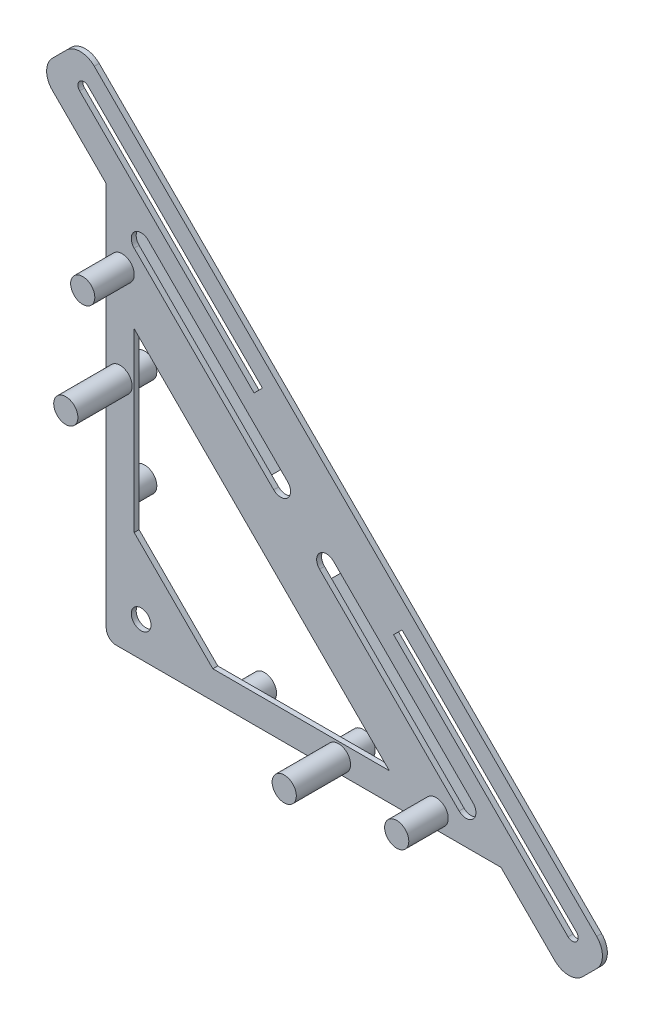
SolidWorks part; units mm, degrees
ref_plane "Front Plane" through (0, 0, 0) normal (0, 0, 1) x (1, 0, 0)
ref_plane "Top Plane" through (0, 0, 0) normal (0, 1, 0) x (1, 0, 0)
ref_plane "Right Plane" through (0, 0, 0) normal (1, 0, 0) x (0, 0, -1)
sketch "Sketch1" plane through (0, 0, 0) normal (0, 0, 1) x (1, 0, 0)
  line L0 (-2000, -2000) -> (2000, 2000) construction
  line L5 (-2000, 2000) -> (2000, -2000) construction
  line L6 (1646.4466, -1646.4466) -> (232.233, -232.233) construction
  line L7 (-1151.4719, 2000) -> (2000, 2000) construction
  line L8 (-2000, 2000) -> (-2000, -1900)
  line L9 (-1900, -2000) -> (2000, -2000)
  line L10 (2000, 2000) -> (2000, -1151.4719) construction
  line L11 (1575.7359, -1717.1573) -> (161.5224, -302.9437)
  line L12 (1717.1573, -1575.7359) -> (302.9437, -161.5224)
  line L22 (-232.233, 232.233) -> (-1646.4466, 1646.4466) construction
  line L25 (-302.9437, 161.5224) -> (-1717.1573, 1575.7359)
  line L26 (-161.5224, 302.9437) -> (-1575.7359, 1717.1573)
  line L27 (-919.6597, -1717.1573) -> (868.6292, -1717.1573)
  line L28 (-919.6597, -1717.1573) -> (-1717.1573, -919.6597)
  line L29 (868.6292, -1717.1573) -> (-1717.1573, 868.6292)
  line L30 (-1717.1573, -919.6597) -> (-1717.1573, 868.6292)
  line L31 (1717.1573, -868.6292) -> (-868.6292, 1717.1573)
  line L32 (1717.1573, 919.6597) -> (1717.1573, -868.6292) construction
  line L33 (1717.1573, 919.6597) -> (919.6597, 1717.1573) construction
  line L34 (919.6597, 1717.1573) -> (-868.6292, 1717.1573) construction
  line L35 (2000, -2000) -> (2687.0058, -2687.0058)
  line L36 (2687.0058, -2687.0058) -> (3111.2698, -2262.7417)
  line L37 (3111.2698, -2262.7417) -> (2000, -1151.4719)
  line L38 (-2000, 2000) -> (-2687.0058, 2687.0058)
  line L39 (-2687.0058, 2687.0058) -> (-2262.7417, 3111.2698)
  line L40 (-2262.7417, 3111.2698) -> (-1151.4719, 2000)
  line L41 (2000, -1151.4719) -> (1717.1573, -868.6292)
  line L42 (-868.6292, 1717.1573) -> (-1151.4719, 2000)
  circle A12 centre (-1646.4466, -1646.4466) radius 100
  circle A13 centre (1646.4466, 1646.4466) radius 100 construction
  arc A14 (1575.7359, -1717.1573) -> (1717.1573, -1575.7359) centre (1646.4466, -1646.4466) ccw
  arc A15 (302.9437, -161.5224) -> (161.5224, -302.9437) centre (232.233, -232.233) ccw
  arc A16 (-302.9437, 161.5224) -> (-161.5224, 302.9437) centre (-232.233, 232.233) ccw
  arc A17 (-1575.7359, 1717.1573) -> (-1717.1573, 1575.7359) centre (-1646.4466, 1646.4466) ccw
  arc A18 (-1900, -2000) -> (-2000, -1900) centre (-1900, -1900) cw
  point P0 (0, 0)
  point P6 (0, 0)
  point P13 (939.3398, -939.3398)
  point P18 (-939.3398, 939.3398)
  point P30 (-424.2641, -424.2641)
  point P31 (-1318.4085, -1318.4085)
  dimension "D5" = 200
  dimension "D8" = 500
  dimension "D6" = 200
  dimension "D1" = 2000
  dimension "D2" = 2000
  dimension "D7" = 500
  dimension "D13" = 100
  dimension "D14" = 100
  dimension "D18" = 100
  dimension "D3" = 4000
  dimension "D4" = 4000
  dimension "D9" = 500
  dimension "D10" = 500
  dimension "D11" = 2000
  dimension "D12" = 2000
  dimension "D15" = 600
  dimension "D16" = 600
  dimension "D17" = 3800
extrude "Boss-Extrude1" add sketch "Sketch1" along normal blind 50
sketch "Sketch3" plane through (0, 0, 0) normal (0, 0, -1) x (-1, 0, 0)
  line L0 (1900, -2000) -> (-2000, -2000) construction
  line L1 (2000, 2000) -> (2000, -1900) construction
  line L2 (1858.5786, 1575.7359) -> (444.3651, 161.5224)
  line L3 (444.3651, 161.5224) -> (479.7204, 126.167)
  line L4 (479.7204, 126.167) -> (1893.934, 1540.3806)
  line L5 (1893.934, 1540.3806) -> (1858.5786, 1575.7359)
  line L6 (1717.1573, 1575.7359) -> (302.9437, 161.5224) construction
  line L7 (-2000, 2000) -> (2000, -2000) construction
  line L8 (-1540.3806, -1893.934) -> (-1575.7359, -1858.5786)
  line L9 (-126.167, -479.7204) -> (-1540.3806, -1893.934)
  line L10 (-1575.7359, -1858.5786) -> (-161.5224, -444.3651)
  line L11 (-161.5224, -444.3651) -> (-126.167, -479.7204)
  circle A0 centre (646.4466, -1860) radius 122.5
  circle A1 centre (-353.5534, -1860) radius 122.5
  circle A3 centre (1860, -646.4466) radius 122.5
  circle A4 centre (1860, 353.5534) radius 122.5
  circle A6 centre (1646.4466, -1646.4466) radius 100 construction
  dimension "D1" = 245
  dimension "D2" = 245
  dimension "D6" = 140
  dimension "D7" = 1000
  dimension "D9" = 100
  dimension "D10" = 245
  dimension "D11" = 245
  dimension "D12" = 140
  dimension "D14" = 1000
  dimension "D4" = 2000
  dimension "D5" = 1000
  dimension "D8" = 50
  dimension "D13" = 1000
extrude "Boss-Extrude3" add sketch "Sketch3" along normal blind 200
extrude "Boss-Extrude4" add sketch "Sketch3<2>" against normal blind 600 contours A4 | A1
sketch "Sketch3<2>" plane through (0, 0, 0) normal (0, 0, -1) x (-1, 0, 0) same geometry as "Sketch3"
sketch "Sketch6" plane through (0, 0, 50) normal (0, 0, 1) x (1, 0, 0)
  line L0 (-2000, -2000) -> (2000, 2000) construction
  line L1 (868.6292, -1717.1573) -> (-1717.1573, 868.6292) construction
  circle A0 centre (-1838.4776, 1343.5029) radius 122.5
  circle A1 centre (1343.5029, -1838.4776) radius 122.5
  dimension "D1" = 245
  dimension "D2" = 245
  dimension "D3" = 2250
  dimension "D4" = 2250
  dimension "D5" = 250
  dimension "D6" = 250
extrude "Boss-Extrude5" add sketch "Sketch6" along normal blind 400
sketch "Sketch8" plane through (0, 0, 50) normal (0, 0, 1) x (1, 0, 0)
  line L0 (-2000, -2000) -> (2000, 2000) construction
  line L3 (-2000, 2000) -> (2000, -2000) construction
  line L4 (-2227.3864, 2722.3611) -> (2722.3611, -2227.3864) construction
  line L5 (-2269.8605, 2679.887) -> (-502.0935, 912.12)
  line L6 (-2184.9122, 2764.8352) -> (-417.1453, 997.0683)
  line L7 (912.12, -502.0935) -> (997.0683, -417.1453)
  line L8 (-502.0935, 912.12) -> (-417.1453, 997.0683)
  line L9 (912.12, -502.0935) -> (2679.887, -2269.8605)
  line L10 (997.0683, -417.1453) -> (2764.8352, -2184.9122)
  arc A2 (-2269.8605, 2679.887) -> (-2184.9122, 2764.8352) centre (-2227.3864, 2722.3611) cw
  arc A3 (2764.8352, -2184.9122) -> (2679.887, -2269.8605) centre (2722.3611, -2227.3864) cw
  point P13 (247.4874, 247.4874)
  dimension "D1" = 7000
  dimension "D2" = 0
  dimension "D3" = 350
  dimension "D4" = 1000
  dimension "D5" = 1000
extrude "Cut-Extrude1" cut sketch "Sketch8" against normal through all
fillet "Fillet1" radius 200 4 edges at (-2687.0058, 2687.0058, 25) (-2262.7417, 3111.2698, 25) (3111.2698, -2262.7417, 25) (2687.0058, -2687.0058, 25)
